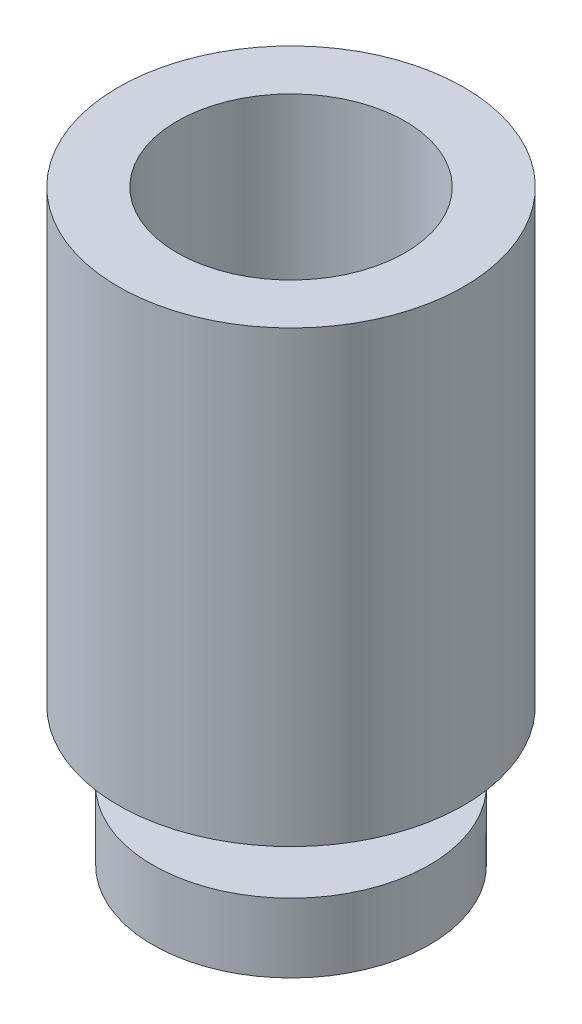
SolidWorks part; units mm, degrees
ref_plane "Front Plane" through (0, 0, 0) normal (0, 0, 1) x (1, 0, 0)
ref_plane "Top Plane" through (0, 0, 0) normal (0, 1, 0) x (1, 0, 0)
ref_plane "Right Plane" through (0, 0, 0) normal (1, 0, 0) x (0, 0, -1)
sketch "Sketch1" plane through (0, 0, 0) normal (0, 1, 0) x (1, 0, 0)
  circle A0 centre (-0.522, 0.5111) radius 2
  circle A1 centre (-0.522, 0.5111) radius 2.5
  dimension "D1" = 4
  dimension "D2" = 5
extrude "Boss-Extrude1" add sketch "Sketch1" along normal blind 6.5 contours A1
extrude "Boss-Extrude2" add sketch "Sketch1<3>" along normal blind 1 contours A0 region at (-0.522, 0, -0.5111)
sketch "Sketch1<3>" plane through (0, 0, 0) normal (0, 1, 0) x (1, 0, 0) same geometry as "Sketch1"
sketch "Sketch5" plane through (0, 0, 0) normal (0, -1, 0) x (1, 0, 0)
  circle A2 centre (-0.522, -0.5111) radius 1
  circle A3 centre (-0.522, -0.5111) radius 1
  dimension "D2" = 2
  dimension "D1" = 1.5
extrude "Boss-Extrude3" add sketch "Sketch5" along normal blind 1 contours A3
sketch "Sketch6" plane through (0, -1, 0) normal (0, -1, 0) x (1, 0, 0)
  circle A0 centre (-0.522, -0.5111) radius 2
  dimension "D1" = 4
extrude "Boss-Extrude4" add sketch "Sketch6" along normal blind 1
sketch "Sketch8" plane through (0, -2, 0) normal (0, -1, 0) x (-1, 0, 0)
  circle A0 centre (0.522, 0.5111) radius 1.5
  dimension "D1" = 3
sketch "Sketch11" plane through (0, 6.5, 0) normal (0, 1, 0) x (1, 0, 0)
  text T0 "VIII" font "Century Gothic" height in points 5
sketch "Sketch12" plane through (0, 6.5, 0) normal (0, 1, 0) x (1, 0, 0)
  circle A0 centre (-0.522, 0.5111) radius 1.65
extrude "Cut-Extrude1" cut sketch "Sketch12" against normal blind 5
